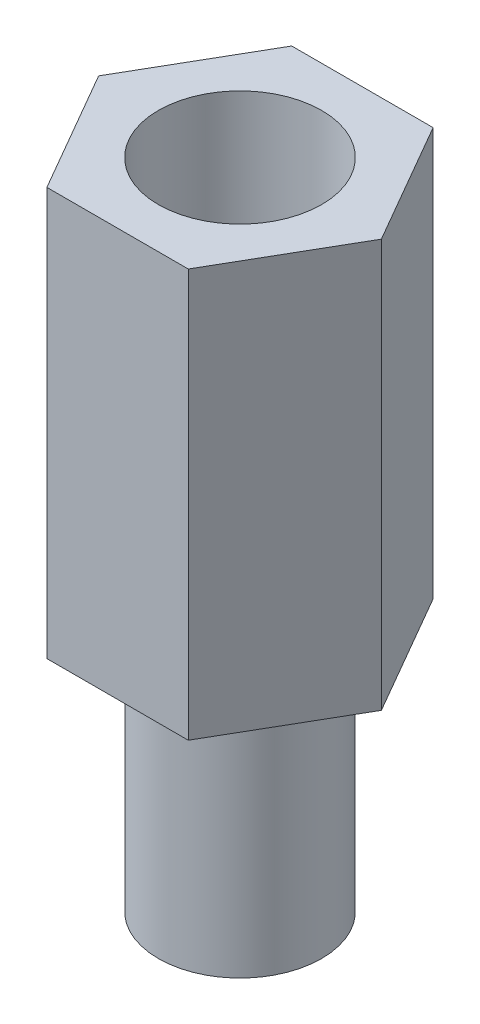
SolidWorks part; units mm, degrees
material "铜"
ref_plane "前视基准面" through (0, 0, 0) normal (0, 0, 1) x (1, 0, 0)
ref_plane "上视基准面" through (0, 0, 0) normal (0, 1, 0) x (1, 0, 0)
ref_plane "右视基准面" through (0, 0, 0) normal (1, 0, 0) x (0, 0, -1)
sketch "草图2" plane through (0, 0, 0) normal (0, 1, 0) x (1, 0, 0)
  line L1 (3.4641, 0) -> (1.7321, 3)
  line L2 (1.7321, 3) -> (-1.7321, 3)
  line L3 (-1.7321, 3) -> (-3.4641, 0)
  line L4 (-3.4641, 0) -> (-1.7321, -3)
  line L5 (-1.7321, -3) -> (1.7321, -3)
  line L6 (1.7321, -3) -> (3.4641, 0)
  circle A0 centre (0, 0) radius 3 construction
  circle A1 centre (0, 0) radius 2
  dimension "D2" = 4
  dimension "D1" = 6
extrude "凸台-拉伸1" add sketch "草图2" along normal blind 10
extrude "凸台-拉伸2" add sketch "草图2<2>" against normal blind 6 separate body contours A1 region at (0, 0, 0)
sketch "草图2<2>" plane through (0, 0, 0) normal (0, 1, 0) x (1, 0, 0) same geometry as "草图2"
